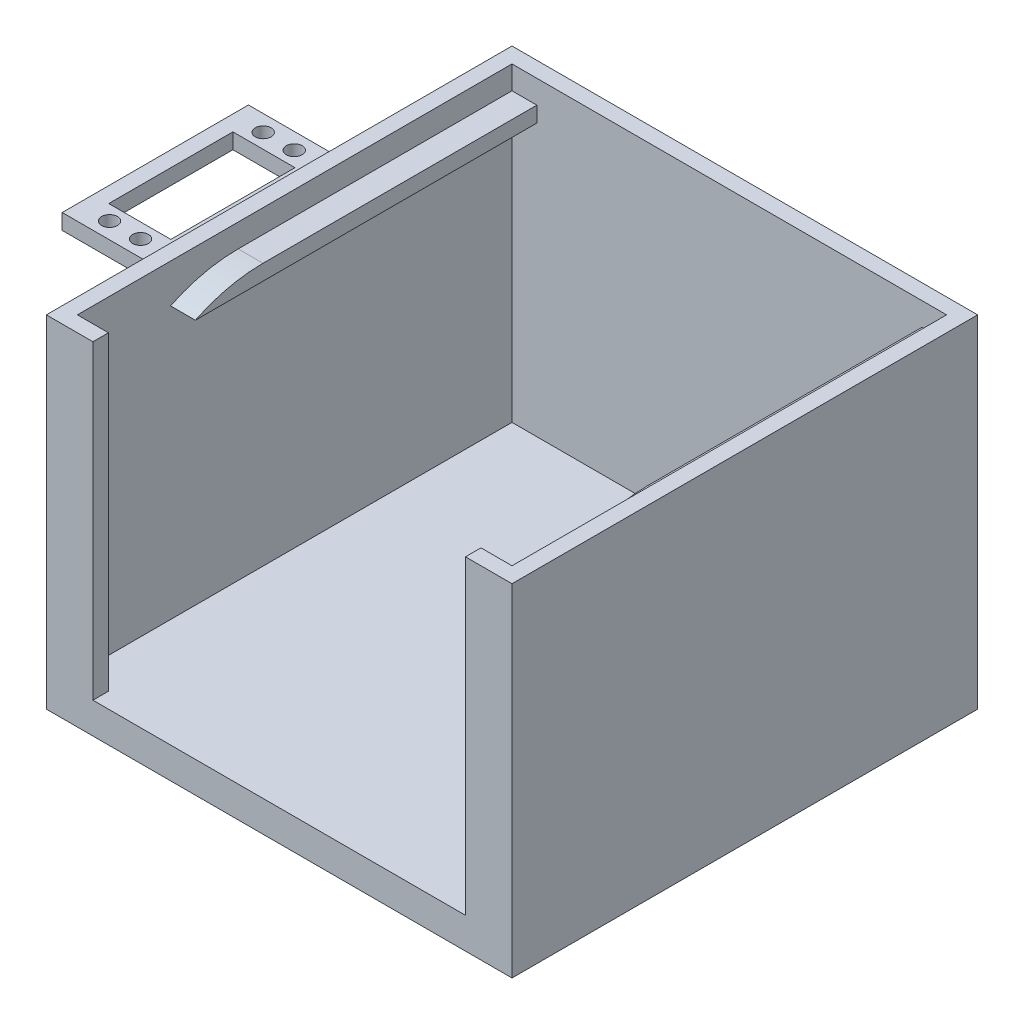
SolidWorks part; units mm, degrees
ref_plane "Front Plane" through (0, 0, 0) normal (0, 0, 1) x (1, 0, 0)
ref_plane "Top Plane" through (0, 0, 0) normal (0, 1, 0) x (1, 0, 0)
ref_plane "Right Plane" through (0, 0, 0) normal (1, 0, 0) x (0, 0, -1)
sketch "Sketch1" plane through (0, 0, 0) normal (0, 1, 0) x (1, 0, 0)
  line L1 (-75, -75) -> (75, -75)
  line L2 (-75, -75) -> (-75, 75)
  line L3 (-75, 75) -> (75, 75)
  line L4 (75, -75) -> (75, 75)
  line L5 (-75, -75) -> (75, 75) construction
  line L6 (-75, 75) -> (75, -75) construction
  point P0 (0, 0)
  dimension "D1" = 150
  dimension "D2" = 150
extrude "Boss-Extrude1" add sketch "Sketch1" along normal blind 10
sketch "Sketch2" plane through (0, 10, 0) normal (0, 1, 0) x (1, 0, 0)
  line L0 (-75, 75) -> (75, -75) construction
  line L1 (75, -75) -> (60, -75) construction
  line L2 (-60, -75) -> (-75, -75) construction
  line L4 (70, -70) -> (60, -70) construction
  line L5 (-60, -70) -> (-70, -70) construction
  line L6 (-75, -75) -> (-75, -60) construction
  line L7 (-75, -30) -> (-75, 75) construction
  line L8 (-70, -70) -> (-70, -60) construction
  line L9 (-70, -30) -> (-70, 70) construction
  line L10 (-75, 75) -> (75, 75)
  line L11 (75, 75) -> (75, -75)
  line L12 (75, -70) -> (75, 30) construction
  line L13 (75, 60) -> (75, 75) construction
  line L14 (70, -70) -> (70, 30) construction
  line L15 (70, 60) -> (70, 70) construction
  line L16 (75, 75) -> (-35, 75) construction
  line L17 (-35, 75) -> (-75, 75) construction
  line L18 (70, 70) -> (-70, 70) construction
  line L19 (70, 70) -> (70, -70)
  line L21 (-60, -70) -> (-60, -75) construction
  line L22 (60, -70) -> (60, -75) construction
  line L23 (-75, 75) -> (-75, -75)
  line L24 (-70, -60) -> (-75, -60) construction
  line L25 (-70, -30) -> (-75, -30) construction
  line L26 (-75, -75) -> (75, 75) construction
  line L35 (70, 70) -> (-70, 70)
  line L39 (-75, -75) -> (-60, -75)
  line L40 (-60, -75) -> (-60, -70)
  line L41 (-60, -70) -> (-70, -70)
  line L44 (60, -70) -> (60, -75)
  line L45 (60, -75) -> (75, -75)
  line L49 (70, -70) -> (60, -70)
  line L54 (-70, 70) -> (-70, -70)
  dimension "D1" = 150
  dimension "D2" = 150
  dimension "D3" = 140
  dimension "D4" = 140
  dimension "D5" = 15
  dimension "D6" = 15
  dimension "D7" = 10
  dimension "D8" = 5
  dimension "D9" = 75
  dimension "D10" = 75
  dimension "D11" = 70
extrude "Boss-Extrude2" add sketch "Sketch2" along normal blind 100
ref_plane "Plane2" through (0, 110, 0) normal (0, 1, 0) x (1, 0, 0)
sketch "Sketch8" plane through (-75, 0, 0) normal (-1, 0, 0) x (0, 0, 1)
  line L0 (-75, 110) -> (75, 0) construction
  line L1 (-75, 0) -> (75, 110) construction
  line L2 (-75, 110) -> (75, 110) construction
  line L6 (0, 110) -> (0, 55) construction
  line L12 (0, 114.3) -> (0, 110) construction
  line L16 (82.5, 110) -> (-82.5, 110) construction
  line L23 (29.9, 114.3) -> (0, 114.3) construction
  line L24 (-10.1, 106) -> (-10.1, 77.3) construction
  line L25 (29.9, 121.4) -> (29.9, 114.3) construction
  line L26 (37.6512, 106) -> (37.6512, 108.5) construction
  line L27 (37.6512, 108.5) -> (29.9, 108.5) construction
  line L28 (-10.1, 77.3) -> (29.9, 77.3) construction
  line L29 (9.9, 121.4) -> (9.9, 77.3) construction
  line L30 (29.9, 77.3) -> (29.9, 106) construction
  line L31 (29.9, 106) -> (37.6512, 106) construction
  line L32 (-10.1, 106) -> (-17.8512, 106) construction
  line L33 (-17.8512, 108.5) -> (-10.1, 108.5) construction
  line L34 (29.9, 108.5) -> (29.9, 114.3) construction
  line L35 (-10.1, 114.3) -> (-10.1, 108.5) construction
  line L37 (-10.1, 121.4) -> (29.9, 121.4) construction
  line L38 (-10.1, 114.3) -> (-10.1, 121.4) construction
  line L39 (0, 114.3) -> (0, 121.4) construction
  line L40 (-17.8512, 106) -> (-17.8512, 108.5) construction
  line L41 (-10.1, 77.3) -> (29.9, 77.3) construction
  line L42 (29.9, 77.3) -> (29.9, 72.3) construction
  line L44 (-10.1, 72.3) -> (-10.1, 77.3) construction
  line L49 (-10.1, 72.3) -> (29.9, 72.3) construction
  line L50 (9.9, 106) -> (39.9, 106)
  line L51 (39.9, 106) -> (39.9, 101)
  line L52 (39.9, 101) -> (-20.1, 101)
  line L53 (-20.1, 101) -> (-20.1, 106)
  line L54 (-20.1, 106) -> (9.9, 106)
  dimension "D3" = 40
  dimension "D4" = 5
extrude "Boss-Extrude3" add sketch "Sketch8" along normal blind 30
sketch "Sketch9" plane through (0, 106, 0) normal (0, 1, 0) x (1, 0, 0)
  line L0 (-105, -9.9) -> (-75, -9.9) construction
  line L9 (-105, -39.9) -> (-105, 20.1) construction
  line L10 (-100, 10.1) -> (-100, 17.35) construction
  line L11 (-100, -29.9) -> (-80, -29.9)
  line L12 (-100, -29.9) -> (-100, 10.1)
  line L13 (-100, 10.1) -> (-80, 10.1)
  line L14 (-80, -29.9) -> (-80, 10.1)
  line L15 (-100, -29.9) -> (-80, 10.1) construction
  line L16 (-100, 10.1) -> (-80, -29.9) construction
  line L17 (-100, 17.35) -> (-80, 17.35) construction
  line L18 (-80, 17.35) -> (-80, 10.1) construction
  line L19 (-90, 10.1) -> (-90, 17.35) construction
  line L20 (-90, 14.85) -> (-90, -34.65) construction
  line L21 (-90, 14.85) -> (-95, 14.85) construction
  line L22 (-75, -39.9) -> (-75, 20.1) construction
  circle A0 centre (-95, 14.85) radius 2.55
  circle A1 centre (-85, 14.85) radius 2.55
  circle A2 centre (-85, -34.65) radius 2.55
  circle A3 centre (-95, -34.65) radius 2.55
  point P6 (-90, -9.9)
  point P13 (-90, -9.9)
  point P24 (-90, -9.9)
  dimension "D4" = 5.1
  dimension "D1" = 20
  dimension "D2" = 40
  dimension "D3" = 49.5
extrude "Cut-Extrude1" cut sketch "Sketch9" against normal blind 5
sketch "Sketch10" plane through (-75, 0, 0) normal (-1, 0, 0) x (0, 0, 1)
  line L0 (-10.1, 77.3) -> (-10.1, 72.3)
  line L2 (29.9, 72.3) -> (29.9, 77.3)
  line L3 (29.9, 77.3) -> (-10.1, 77.3)
  line L8 (-10.1, 72.3) -> (7.4, 72.3)
  line L10 (12.4, 72.3) -> (12.4, 52.3)
  line L11 (12.4, 52.3) -> (7.4, 52.3)
  line L12 (7.4, 52.3) -> (7.4, 72.3)
  line L13 (12.4, 72.3) -> (29.9, 72.3)
  dimension "D1" = 20
  dimension "D2" = 5
  dimension "D3" = 17.5
extrude "Boss-Extrude4" add sketch "Sketch10" along normal blind 25
sketch "Sketch12" plane through (-70, 0, 0) normal (1, 0, 0) x (0, 0, -1)
  line L0 (70, 110) -> (70, 102.5) construction
  line L1 (70, 110) -> (70, 10) construction
  line L2 (70, 102.5) -> (-40, 102.5) construction
  line L3 (-40, 102.5) -> (-40, 97.5) construction
  line L4 (-40, 97.5) -> (70, 97.5) construction
  line L5 (70, 97.5) -> (70, 102.5) construction
  line L7 (-40, 102.5) -> (70, 102.5)
  line L8 (-40, 102.5) -> (-40, 97.5)
  line L9 (-40, 97.5) -> (70, 97.5)
  line L10 (70, 102.5) -> (70, 97.5)
  dimension "D1" = 7.5
  dimension "D2" = 5
  dimension "D3" = 110
extrude "Boss-Extrude5" add sketch "Sketch12" along normal blind 8
mirror "Mirror1" about plane through (0, 0, 0) normal (1, 0, 0) of "Boss-Extrude5"
fillet "Fillet2" radius 50 2 edges at (66, 102.5, 40) (-66, 102.5, 40)
sketch "Sketch13" plane through (0, 0, 12.4) normal (0, 0, 1) x (1, 0, 0)
  line L0 (-100, 52.3) -> (-100, 70.3)
  line L3 (-80, 52.3) -> (-100, 70.3)
  line L4 (-100, 52.3) -> (-80, 52.3)
  line L5 (-100, 52.3) -> (-75, 52.3) construction
  dimension "D1" = 18
extrude "Cut-Extrude3" cut sketch "Sketch13" against normal blind 8
ref_plane "Plane3" through (0, 110, 0) normal (0, 1, 0) x (1, 0, 0)
sketch "Sketch14" plane through (0, 110, 0) normal (0, 1, 0) x (1, 0, 0)
  line L0 (-75, -75) -> (-60, -75)
  line L1 (-60, -75) -> (-60, -70)
  line L2 (-60, -70) -> (-70, -70)
  line L3 (-70, -70) -> (-70, -35)
  line L4 (-70, -70) -> (-70, 70) construction
  line L5 (-70, -35) -> (-75, -35)
  line L6 (-75, -39.9) -> (-75, 20.1) construction
  line L7 (-75, -35) -> (-75, -75)
  line L8 (60, -75) -> (60, -70)
  line L9 (60, -70) -> (60, -75) construction
  line L10 (60, -70) -> (70, -70)
  line L11 (70, -70) -> (70, 70)
  line L12 (70, 70) -> (-70, 70)
  line L13 (-70, 70) -> (-70, 65)
  line L14 (-70, 70) -> (-70, -18.2055) construction
  line L15 (-70, 65) -> (-75, 65)
  line L16 (-75, 75) -> (-75, -75) construction
  line L17 (-75, 65) -> (-75, 75)
  line L18 (-75, 75) -> (75, 75)
  line L19 (75, 75) -> (75, -75)
  line L20 (75, -75) -> (60, -75)
extrude "Boss-Extrude6" add sketch "Sketch14" along normal blind 18
sketch "Sketch15" plane through (0, 128, 0) normal (0, 1, 0) x (1, 0, 0)
  line L1 (-75, -75) -> (75, -75)
  line L2 (-75, -75) -> (-75, 75)
  line L3 (-75, 75) -> (75, 75)
  line L4 (75, -75) -> (75, 75)
extrude "Boss-Extrude7" add sketch "Sketch15" along normal blind 5
sketch "Sketch16" plane through (0, 0, 0) normal (0, 0, 1) x (1, 0, 0)
  line L0 (2.75, 110) -> (-2.75, 110) construction
  line L1 (-75, 110) -> (75, 110)
  line L2 (-75, 110) -> (-75, 133)
  line L3 (-75, 133) -> (75, 133)
  line L4 (75, 110) -> (75, 133)
  line L5 (-75, 133) -> (-75, 0) construction
extrude "Cut-Extrude4" cut sketch "Sketch16" against normal mid plane 150
